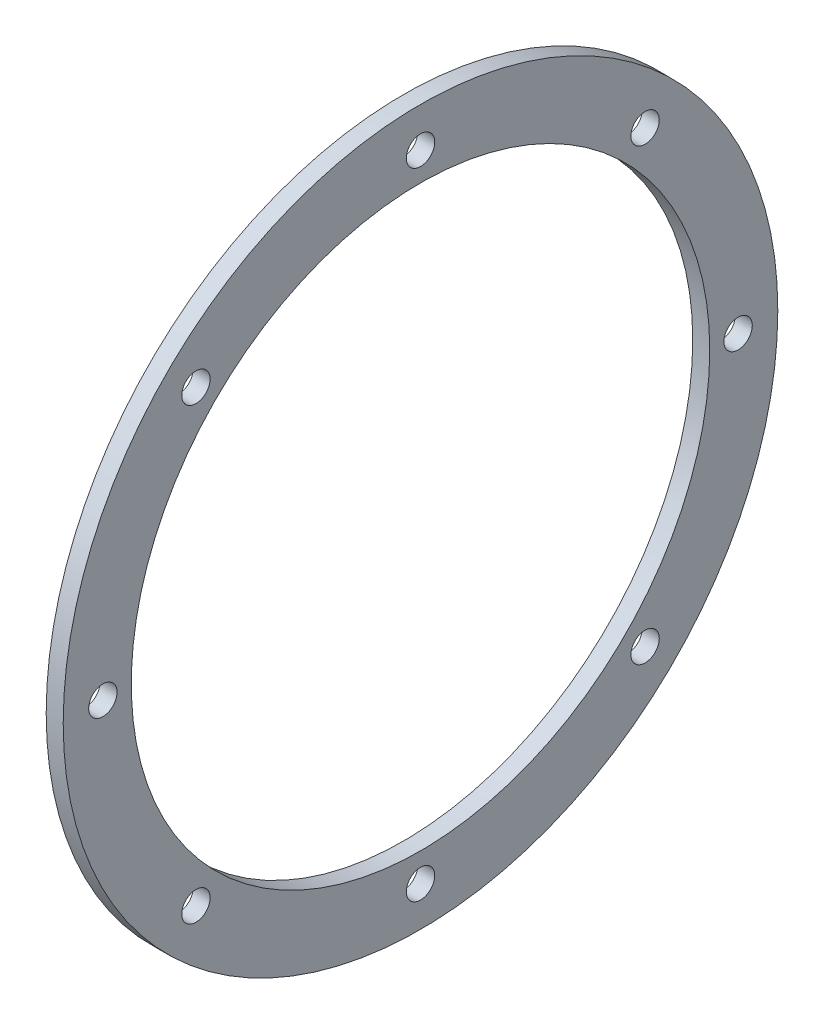
SolidWorks part; units mm, degrees
material "201 Stal nierdzewna odprężona (SS)"
ref_plane "Płaszczyzna przednia" through (0, 0, 0) normal (0, 0, 1) x (1, 0, 0)
ref_plane "Płaszczyzna górna" through (0, 0, 0) normal (0, 1, 0) x (1, 0, 0)
ref_plane "Płaszczyzna prawa" through (0, 0, 0) normal (1, 0, 0) x (0, 0, -1)
sketch "Szkic1" plane through (0, 0, 0) normal (1, 0, 0) x (0, 0, -1)
  circle A0 centre (0, 0) radius 51
  circle A1 centre (0, 0) radius 63
  circle A2 centre (0, 56) radius 2.5
  circle A3 centre (39.598, 39.598) radius 2.5
  circle A4 centre (56, 0) radius 2.5
  circle A5 centre (39.598, -39.598) radius 2.5
  circle A6 centre (0, -56) radius 2.5
  circle A7 centre (-39.598, -39.598) radius 2.5
  circle A8 centre (-56, 0) radius 2.5
  circle A9 centre (-39.598, 39.598) radius 2.5
  point P22 (0, 0)
  dimension "D1" = 102
  dimension "D2" = 126
  dimension "D4" = 5
  dimension "D3" = 56
  dimension "D5" = 8
extrude "Dodanie-wyciągnięcie1" add sketch "Szkic1" along normal blind 3
